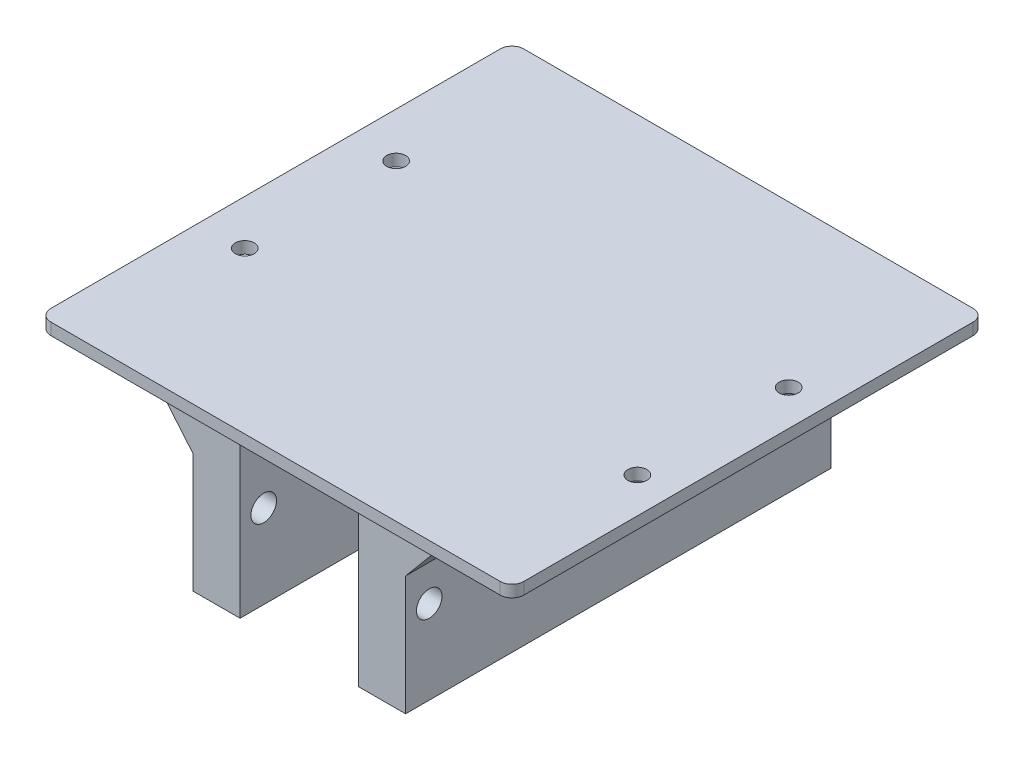
SolidWorks part; units mm, degrees
ref_plane "Front Plane" through (0, 0, 0) normal (0, 0, 1) x (1, 0, 0)
ref_plane "Top Plane" through (0, 0, 0) normal (0, 1, 0) x (1, 0, 0)
ref_plane "Right Plane" through (0, 0, 0) normal (1, 0, 0) x (0, 0, -1)
sketch "Sketch1" plane through (0, 0, 0) normal (0, 1, 0) x (1, 0, 0)
  line L1 (2.5, 0) -> (97.5, 0)
  line L2 (0, 2.5) -> (0, 97.5)
  line L3 (2.5, 100) -> (97.5, 100)
  line L4 (100, 2.5) -> (100, 97.5)
  circle A0 centre (9.5, 34) radius 2
  circle A1 centre (9.5, 66) radius 2
  arc A4 (97.5, 100) -> (100, 97.5) centre (97.5, 97.5) cw
  arc A5 (97.5, 0) -> (100, 2.5) centre (97.5, 2.5) ccw
  arc A6 (2.5, 0) -> (0, 2.5) centre (2.5, 2.5) cw
  arc A7 (0, 97.5) -> (2.5, 100) centre (2.5, 97.5) cw
  circle A8 centre (92.5, 66) radius 2
  circle A9 centre (92.5, 34) radius 2
  point P17 (100, 100)
  point P22 (0, 0)
  point P25 (0, 100)
  dimension "D1" = 4
  dimension "D7" = 2.5
  dimension "D8" = 83
  dimension "D2" = 100
  dimension "D3" = 100
  dimension "D4" = 32
  dimension "D5" = 34
  dimension "D6" = 9.5
extrude "Boss-Extrude1" add sketch "Sketch1" along normal blind 2.5
sketch "Sketch4" plane through (0, 0, 0) normal (0, 1, 0) x (1, 0, 0)
  line L0 (37.5, 50) -> (62.5, 50) construction
  line L1 (27.5, 5) -> (37.5, 5)
  line L2 (27.5, 5) -> (27.5, 95)
  line L3 (27.5, 95) -> (37.5, 95)
  line L4 (37.5, 5) -> (37.5, 95)
  line L5 (62.5, 95) -> (72.5, 95)
  line L6 (62.5, 95) -> (62.5, 5)
  line L7 (62.5, 5) -> (72.5, 5)
  line L8 (72.5, 95) -> (72.5, 5)
  line L9 (50, 100) -> (50, 0) construction
  line L10 (97.5, 100) -> (2.5, 100) construction
  line L11 (2.5, 0) -> (97.5, 0) construction
  point P16 (50, 50)
  point P17 (50, 50)
  dimension "D1" = 25
  dimension "D2" = 5
  dimension "D3" = 10
extrude "Boss-Extrude2" add sketch "Sketch4" against normal blind 36.75
sketch "Sketch5" plane through (27.5, 0, 0) normal (-1, 0, 0) x (0, 0, 1)
  line L0 (-95, -36.75) -> (-95, 0) construction
  line L2 (-95, 0) -> (-5, 0) construction
  circle A0 centre (-90, -19.05) radius 2.7
  circle A1 centre (-50, -19.05) radius 2.7
  circle A2 centre (-10, -19.05) radius 2.7
  dimension "D1" = 40
  dimension "D3" = 5.4
  dimension "D2" = 80
  dimension "D4" = 5
  dimension "D5" = 19.05
extrude "Cut-Extrude1" cut sketch "Sketch5" against normal through all
draft "Draft1" [suppressed] type of draft neutral plane draft angle 5 faces to draft 6 parameters "D1"=5
sketch "Sketch6" plane through (0, 0, -5) normal (0, 0, 1) x (1, 0, 0)
  line L0 (72.5, 0) -> (82.1418, 0)
  line L1 (2.5, 0) -> (97.5, 0) construction
  line L2 (82.1418, 0) -> (72.5, -11.4907)
  line L3 (72.5, -36.75) -> (72.5, 0) construction
  line L4 (72.5, -11.4907) -> (72.5, 0)
  line L5 (27.5, 0) -> (17.8582, 0)
  line L6 (17.8582, 0) -> (27.5, -11.4907)
  line L7 (27.5, -36.75) -> (27.5, 0) construction
  line L8 (27.5, -11.4907) -> (27.5, 0)
  dimension "D1" = 15
  dimension "D2" = 50
extrude "Boss-Extrude3" add sketch "Sketch6" against normal up to surface (90 mm away) from surface up to face at (32.5, -18.375, -95) starting at face at (32.5, -18.375, -5)
